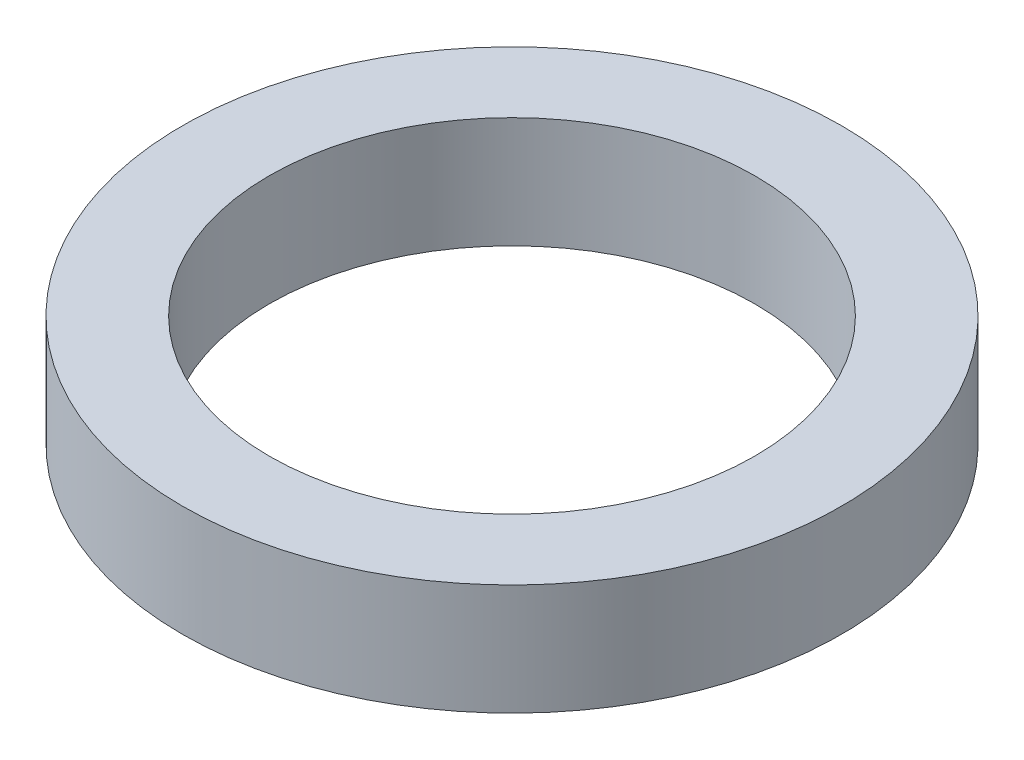
SolidWorks part; units mm, degrees
ref_plane "Front Plane" through (0, 0, 0) normal (0, 0, 1) x (1, 0, 0)
ref_plane "Top Plane" through (0, 0, 0) normal (0, 1, 0) x (1, 0, 0)
ref_plane "Right Plane" through (0, 0, 0) normal (1, 0, 0) x (0, 0, -1)
sketch "Sketch1" plane through (0, 0, 0) normal (0, 1, 0) x (1, 0, 0)
  circle A0 centre (0, 0) radius 47.5
  dimension "FLANGE_OD" = 95
extrude "Boss-Extrude1" add sketch "Sketch1" along normal blind 16
sketch "Sketch2" plane through (0, 0, 0) normal (0, 1, 0) x (1, 0, 0)
  circle A0 centre (0, 0) radius 35
  dimension "BORE_D" = 70
extrude "Cut-Extrude1" cut sketch "Sketch2" along normal through all
sketch "Sketch3" plane through (0, 16, 0) normal (0, 1, 0) x (1, 0, 0)
  circle A0 centre (0, 0) radius 20.8725 construction
  circle A1 centre (-20.8725, 0) radius 1.5312
  dimension "BOLT_D" = 3.0624
  dimension "BOLT_PCD" = 41.7449
extrude "Cut-Extrude2" cut sketch "Sketch3" against normal blind 12.3912 rebuild error yes
pattern_circular "CirPattern1" count 8 over 360 rebuild error yes
